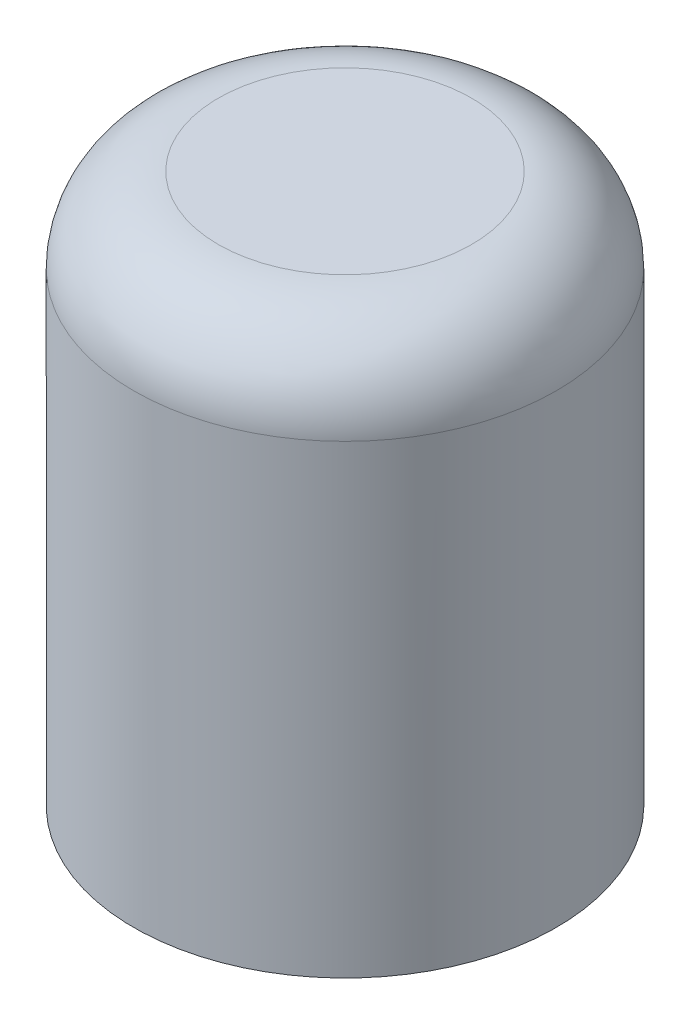
SolidWorks part; units mm, degrees
ref_plane "Front Plane" through (0, 0, 0) normal (0, 0, 1) x (1, 0, 0)
ref_plane "Top Plane" through (0, 0, 0) normal (0, 1, 0) x (1, 0, 0)
ref_plane "Right Plane" through (0, 0, 0) normal (1, 0, 0) x (0, 0, -1)
sketch "Sketch1" plane through (0, 0, 0) normal (0, 1, 0) x (1, 0, 0)
  circle A0 centre (0, 0) radius 5
  dimension "D1" = 10
extrude "Boss-Extrude1" add sketch "Sketch1" along normal blind 13
sketch "Insert" plane through (0, 0, 0) normal (0, -1, 0) x (1, 0, 0)
  line L0 (-1.75, 2.7386) -> (-1.75, -2.7386)
  line L1 (3.25, 0) -> (1.7771, 0) construction
  line L2 (-1.75, 0) -> (-0.8194, 0) construction
  arc A0 (-1.75, -2.7386) -> (-1.75, 2.7386) centre (0, 0) ccw
  dimension "D1" = 6.5
  dimension "D2" = 5
extrude "Cut-Extrude1" cut sketch "Insert" against normal blind 12
fillet "Fillet4" radius 2 2 edges at (3.25, 12, 0) (-1.75, 12, 0) type face fillet first side face at (-1.75, 6, 0) first side face at (0.75, 6, 0) second side face at (0.75, 12, 0)
fillet "Fillet5" radius 0.5 2 edges at (-1.75, 0, 0) (3.25, 0, 0) type face fillet first side face at (0.75, 0, 0) second side face at (0.75, 5, 0) second side face at (-1.75, 5, 0)
fillet "Fillet6" radius 2 1 edges at (0, 13, 5) type face fillet first side face at (0, 13, 5) second side face at (0, 13, 5)
